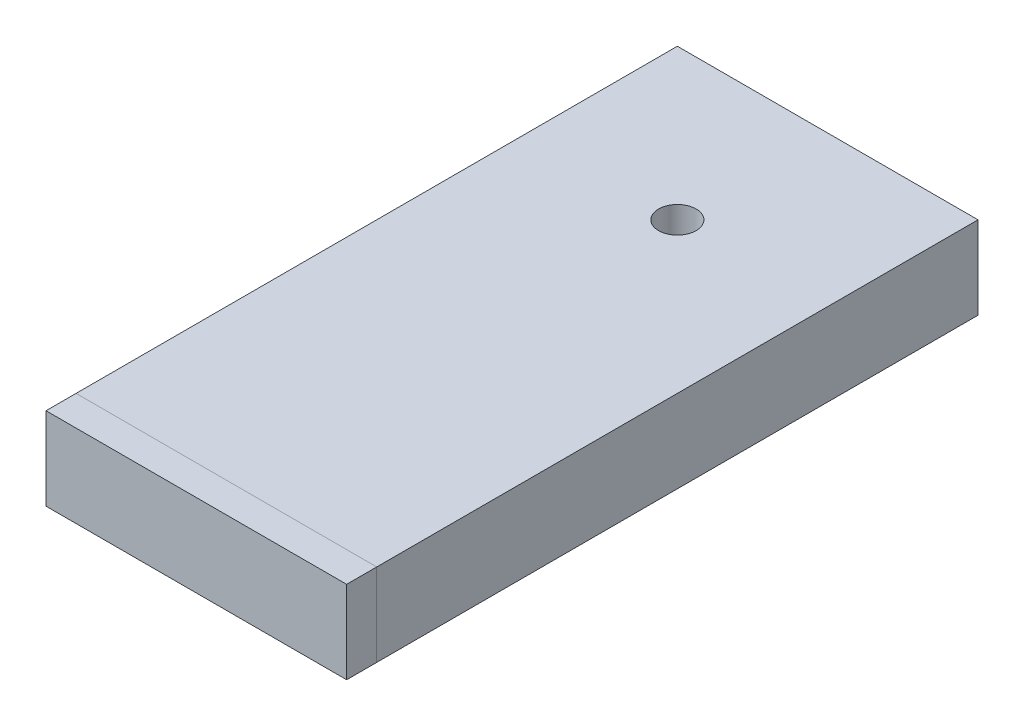
SolidWorks part; units mm, degrees
material "Maple"
ref_plane "Front Plane" through (0, 0, 0) normal (0, 0, 1) x (1, 0, 0)
ref_plane "Top Plane" through (0, 0, 0) normal (0, 1, 0) x (1, 0, 0)
ref_plane "Right Plane" through (0, 0, 0) normal (1, 0, 0) x (0, 0, -1)
sketch "Sketch1" plane through (0, 0, 0) normal (0, 1, 0) x (1, 0, 0)
  line L1 (-31.75, 63.5) -> (31.75, 63.5)
  line L2 (-31.75, 63.5) -> (-31.75, -63.5)
  line L3 (-31.75, -63.5) -> (31.75, -63.5)
  line L4 (31.75, 63.5) -> (31.75, -63.5)
  line L5 (-31.75, 63.5) -> (31.75, -63.5) construction
  line L6 (-31.75, -63.5) -> (31.75, 63.5) construction
  point P0 (0, 0)
  dimension "D1" = 63.5
  dimension "D2" = 127
extrude "Boss-Extrude1" add sketch "Sketch1" along normal blind 19.05
sketch "Sketch2" plane through (0, 19.05, 0) normal (0, 1, 0) x (1, 0, 0)
  line L0 (-31.75, -63.5) -> (31.75, -63.5) construction
  circle A0 centre (0, 31.75) radius 3.9688
  dimension "D1" = 7.9375
  dimension "D2" = 95.25
extrude "Cut-Extrude1" cut sketch "Sketch2" against normal through all
sketch "Sketch3" plane through (0, 0, 63.5) normal (0, 0, 1) x (1, 0, 0)
  line L1 (-31.75, 19.05) -> (31.75, 19.05)
  line L2 (-31.75, 19.05) -> (-31.75, 0)
  line L3 (-31.75, 0) -> (31.75, 0)
  line L4 (31.75, 19.05) -> (31.75, 0)
  line L5 (-31.75, 19.05) -> (31.75, 0) construction
  line L6 (-31.75, 0) -> (31.75, 19.05) construction
  point P0 (0, 9.525)
extrude "Boss-Extrude2" add sketch "Sketch3" along normal blind 6.35 separate body
sketch "Sketch4" plane through (0, 0, -63.5) normal (0, 0, -1) x (-1, 0, 0)
  line L0 (-4.3656, 0) -> (4.3656, 0) construction
  line L1 (-31.75, 0) -> (-4.3656, 0)
  line L2 (-31.75, 0) -> (-31.75, 1.5875)
  line L3 (-31.75, 1.5875) -> (-4.3656, 1.5875)
  line L4 (-4.3656, 0) -> (-4.3656, 1.5875)
  line L5 (4.3656, 1.5875) -> (31.75, 1.5875)
  line L6 (4.3656, 1.5875) -> (4.3656, 0)
  line L7 (4.3656, 0) -> (31.75, 0)
  line L8 (31.75, 1.5875) -> (31.75, 0)
  dimension "D1" = 1.5875
  dimension "D2" = 8.7312
extrude "Cut-Extrude2" cut sketch "Sketch4" against normal through all
sketch "Sketch5" plane through (0, 0, 69.85) normal (0, 0, 1) x (1, 0, 0)
  line L1 (-4.3656, 1.5875) -> (4.3656, 1.5875)
  line L2 (-4.3656, 1.5875) -> (-4.3656, 0)
  line L3 (-4.3656, 0) -> (4.3656, 0)
  line L4 (4.3656, 1.5875) -> (4.3656, 0)
extrude "Cut-Extrude3" cut sketch "Sketch5" against normal up to vertex (6.35 mm away) up to point (-4.3656, 0, 63.5)
